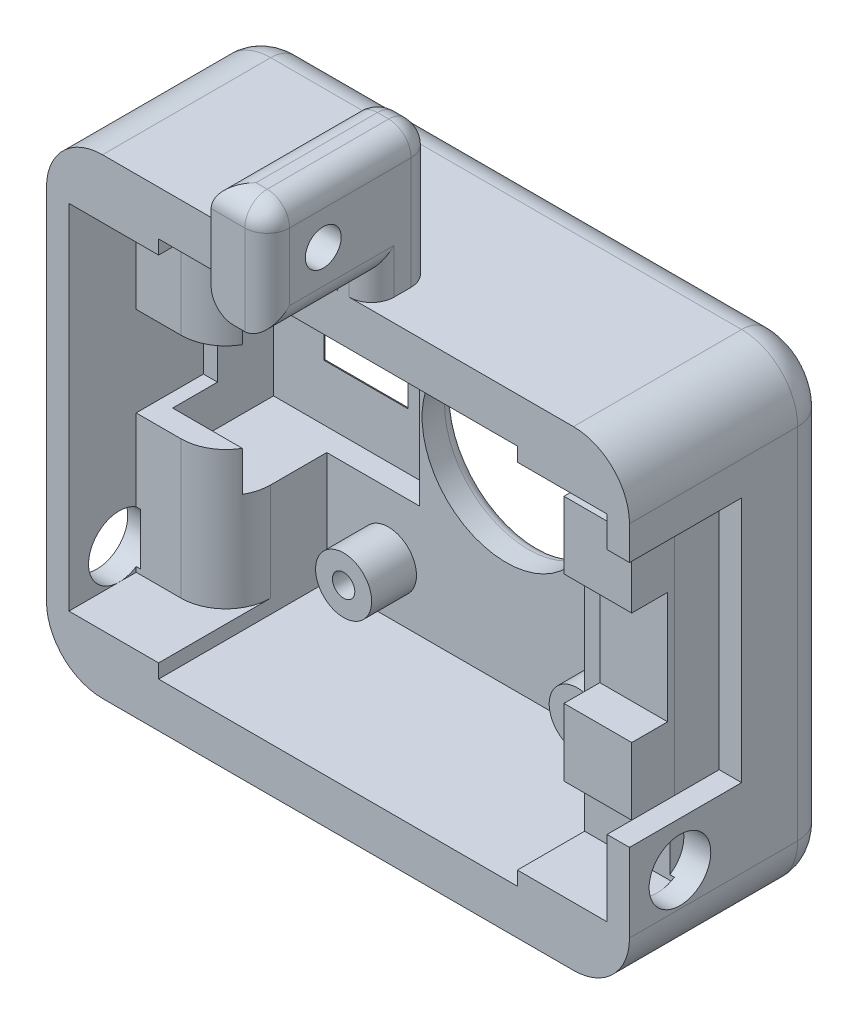
SolidWorks part; units mm, degrees
ref_plane "Front Plane" through (0, 0, 0) normal (0, 0, 1) x (1, 0, 0)
ref_plane "Top Plane" through (0, 0, 0) normal (0, 1, 0) x (1, 0, 0)
ref_plane "Right Plane" through (0, 0, 0) normal (1, 0, 0) x (0, 0, -1)
sketch "Sketch1" plane through (0, 0, 0) normal (0, 0, 1) x (1, 0, 0)
  line L1 (-26, 21) -> (26, 21)
  line L2 (-26, 21) -> (-26, -21)
  line L3 (-26, -21) -> (26, -21)
  line L4 (26, 21) -> (26, -21)
  line L5 (-26, 21) -> (26, -21) construction
  line L6 (-26, -21) -> (26, 21) construction
  point P0 (0, 0)
  dimension "D1" = 42
  dimension "D2" = 52
extrude "Boss-Extrude1" add sketch "Sketch1" along normal blind 10 contours L4 L3 L2 L1
sketch "Sketch2" plane through (0, 0, 10) normal (0, 0, 1) x (1, 0, 0)
  line L0 (-26, 21) -> (26, 21) construction
  line L1 (-24, 15.75) -> (24, 15.75)
  line L2 (-24, 15.75) -> (-24, -15.75)
  line L3 (-24, -15.75) -> (24, -15.75)
  line L4 (24, 15.75) -> (24, -15.75)
  line L5 (-24, 15.75) -> (24, -15.75) construction
  line L6 (-24, -15.75) -> (24, 15.75) construction
  line L7 (-26, -21) -> (26, -21) construction
  point P0 (0, 0)
  dimension "D1" = 5.25
  dimension "D2" = 48
  dimension "D3" = 5.25
extrude "Cut-Extrude1" cut sketch "Sketch2" against normal blind 6
sketch "Sketch6" plane through (0, 0, 0) normal (0, 0, -1) x (-1, 0, 0)
  line L1 (-26, 21) -> (26, 21)
  line L2 (-26, 21) -> (-26, -21)
  line L3 (-26, -21) -> (26, -21)
  line L4 (26, 21) -> (26, -21)
  line L5 (-26, 21) -> (26, -21) construction
  line L6 (-26, -21) -> (26, 21) construction
  point P0 (0, 0)
  dimension "D1" = 52
  dimension "D2" = 42
extrude "Boss-Extrude2" add sketch "Sketch6" along normal blind 8
sketch "Sketch5" plane through (0, 0, 4) normal (0, 0, 1) x (1, 0, 0)
  line L1 (-16, 17) -> (16, 17)
  line L2 (-16, 17) -> (-16, -17)
  line L3 (-16, -17) -> (16, -17)
  line L4 (16, 17) -> (16, -17)
  line L5 (-16, 17) -> (16, -17) construction
  line L6 (-16, -17) -> (16, 17) construction
  point P0 (0, 0)
  dimension "D1" = 34
  dimension "D2" = 32
extrude "Cut-Extrude5" cut sketch "Sketch5" against normal blind 9 and the other way through all
sketch "Sketch7" plane through (0, 0, -5) normal (0, 0, 1) x (1, 0, 0)
  circle A0 centre (0, 0) radius 7.5
  dimension "D1" = 15
extrude "Cut-Extrude4" cut sketch "Sketch7" against normal up to next
fillet "Fillet2" radius 1 1 edges at (-7.5, 0, -8)
fillet "Fillet3" radius 3 4 edges at (0, -21, -8) (-26, 0, -8) (26, 0, -8) (0, 21, -8)
fillet "Fillet4" radius 5 8 edges at (25.1213, 20.1213, -7.1213) (-25.1213, 20.1213, -7.1213) (-25.1213, -20.1213, -7.1213) (25.1213, -20.1213, -7.1213) (-26, 21, 2.5) (-26, -21, 2.5) (26, -21, 2.5) (26, 21, 2.5)
sketch "Sketch8" plane through (0, 0, 10) normal (0, 0, 1) x (1, 0, 0)
  line L0 (24, -15.75) -> (24, 15.75) construction
  line L5 (24, 13) -> (26, 13)
  line L6 (24, 13) -> (24, -9)
  line L7 (24, -9) -> (26, -9)
  line L8 (26, 13) -> (26, -9)
  line L9 (26, 16) -> (26, -16) construction
  line L10 (-21, 21) -> (21, 21) construction
  dimension "D1" = 22
  dimension "D2" = 8
extrude "Cut-Extrude6" cut sketch "Sketch8" against normal blind 10
sketch "Sketch11" plane through (0, 0, 4) normal (0, 0, 1) x (1, 0, 0)
  line L1 (24, 13) -> (17.954, 13)
  line L2 (24, 13) -> (24, -9)
  line L3 (24, -9) -> (17.954, -9)
  line L4 (17.954, 13) -> (17.954, -9)
  dimension "D1" = 6.046
  dimension "D2" = 22
extrude "Boss-Extrude9" add sketch "Sketch11" along normal blind 3.8 separate body
sketch "Sketch12" plane through (0, 0, 7.8) normal (0, 0, 1) x (1, 0, 0)
  line L0 (24, -9) -> (24, 13) construction
  line L1 (24, 7) -> (16.5, 7)
  line L2 (24, 7) -> (24, -3)
  line L3 (24, -3) -> (16.5, -3)
  line L4 (16.5, 7) -> (16.5, -3)
  line L5 (24, 13) -> (17.954, 13) construction
  line L7 (17.954, -9) -> (24, -9) construction
  dimension "D1" = 10
  dimension "D2" = 6
  dimension "D3" = 6
  dimension "D4" = 7.5
extrude "Cut-Extrude8" cut sketch "Sketch12" against normal blind 3.2
fillet "Fillet9" radius 4 1 edges at (-16, 0, 4)
sketch "Sketch13" plane through (26, 0, 0) normal (1, 0, 0) x (0, 0, -1)
  line L1 (-10, -9) -> (-10, -16) construction
  line L4 (-10, -16) -> (5, -16) construction
  circle A0 centre (-5.5, -13) radius 2.75
  dimension "D1" = 5.5
  dimension "D2" = 3
  dimension "D3" = 4.5
extrude "Cut-Extrude9" cut sketch "Sketch13" against normal blind 2.4
sketch "Sketch14" plane through (-26, 0, 0) normal (-1, 0, 0) x (0, 0, 1)
  line L1 (10, 16) -> (10, -16) construction
  line L2 (-5, -16) -> (10, -16) construction
  circle A0 centre (5.5, -13) radius 2.75
  dimension "D1" = 5.5
  dimension "D2" = 3
  dimension "D3" = 4.5
extrude "Cut-Extrude10" cut sketch "Sketch14" against normal blind 2.4
ref_plane "Plane2" through (0, 0, 2) normal (0, 0, -1) x (-1, 0, 0)
sketch "Sketch18" plane through (0, 0, 2) normal (0, 0, -1) x (-1, 0, 0)
  line L1 (-22.75, 7) -> (-7.75, 7)
  line L2 (-22.75, 7) -> (-22.75, -7)
  line L3 (-22.75, -7) -> (-7.75, -7)
  line L4 (-7.75, 7) -> (-7.75, -7)
  line L8 (7.75, 7) -> (22.75, 7)
  line L9 (7.75, 7) -> (7.75, -7)
  line L10 (7.75, -7) -> (22.75, -7)
  line L11 (22.75, 7) -> (22.75, -7)
  point P4 (-7.75, 0)
  dimension "D1" = 15
  dimension "D2" = 14
  dimension "D3" = 7.75
  dimension "D5" = 15
  dimension "D6" = 14
  dimension "D8" = 7.75
extrude "Cut-Extrude15" cut sketch "Sketch18" along normal blind 9
sketch "Sketch19" plane through (0, 0, -7) normal (0, 0, 1) x (1, 0, 0)
  line L1 (10.75, 2) -> (18.25, 2)
  line L2 (10.75, 2) -> (10.75, -2)
  line L3 (10.75, -2) -> (18.25, -2)
  line L4 (18.25, 2) -> (18.25, -2)
  line L7 (-18.25, 2) -> (-10.75, 2)
  line L8 (-18.25, 2) -> (-18.25, -2)
  line L9 (-18.25, -2) -> (-10.75, -2)
  line L10 (-10.75, 2) -> (-10.75, -2)
  line L12 (-7.75, 7) -> (-7.75, -7) construction
  line L13 (7.75, -7) -> (7.75, 7) construction
  point P6 (-10.75, 0)
  dimension "D1" = 7.5
  dimension "D2" = 4
  dimension "D3" = 3
  dimension "D5" = 7.5
  dimension "D6" = 4
  dimension "D7" = 3
extrude "Cut-Extrude16" cut sketch "Sketch19" against normal up to next (1 mm away)
sketch "Sketch21" plane through (0, 21, 0) normal (0, 1, 0) x (1, 0, 0)
  line L0 (-21, -10) -> (21, -10) construction
  line L1 (-2, -4.4799) -> (3, -4.4799)
  line L2 (-2, -4.4799) -> (-2, -10)
  line L3 (-2, -10) -> (3, -10)
  line L4 (3, -4.4799) -> (3, -10)
  line L5 (-26, -10) -> (-26, 5) construction
  dimension "D1" = 5
  dimension "D2" = 24
extrude "Boss-Extrude10" add sketch "Sketch21" along normal blind 2
sketch "Sketch27" plane through (0, 23, 0) normal (0, 1, 0) x (1, 0, 0)
  line L0 (-2, -4.4799) -> (-2, -10) construction
  line L1 (-2, -4.4799) -> (3, -4.4799)
  line L2 (-2, -4.4799) -> (-2, -19.3143)
  line L3 (-2, -19.3143) -> (3, -19.3143)
  line L4 (3, -4.4799) -> (3, -19.3143)
  line L5 (-2, -4.4799) -> (-2, -10) construction
  dimension "D1" = 14.8343
  dimension "D2" = 5
extrude "Boss-Extrude13" add sketch "Sketch27" along normal blind 10
sketch "Sketch28" plane through (-2, 0, 0) normal (-1, 0, 0) x (0, 0, 1)
  line L2 (19.3143, 33) -> (19.3143, 23) construction
  circle A0 centre (14.3143, 28) radius 1.6
  point P10 (19.3143, 28)
  dimension "D1" = 3.2
  dimension "D2" = 5
extrude "Cut-Extrude19" cut sketch "Sketch28" against normal through all
fillet "Fillet14" radius 2 11 edges at (0.5, 33, 4.4799) (3, 33, 11.8971) (0.5, 33, 19.3143) (-2, 33, 11.8971) (3, 27, 4.4799) (3, 28, 19.3143) (-2, 22, 10) (-2, 23, 14.6571) (-2, 27, 4.4799) (3, 23, 14.6571) (3, 22, 10)
fillet "Fillet13" radius 2 8 edges at (-18.25, 0, -8) (-10.75, 0, -8) (-14.5, -2, -8) (-14.5, 2, -8) (10.75, 0, -8) (18.25, 0, -8) (14.5, -2, -8) (14.5, 2, -8)
sketch "Sketch25" plane through (0, 0, -5) normal (0, 0, 1) x (1, 0, 0)
  line L0 (-10.5, 12.5) -> (10.5, 12.5) construction
  circle A0 centre (-10.5, 12.5) radius 2.5
  circle A1 centre (10.5, 12.5) radius 2.5
  circle A3 centre (-10.5, -12.5) radius 2.5
  circle A4 centre (10.3376, -12.5) radius 2.5
  point P4 (0, 12.5)
  dimension "D3" = 5
  dimension "D4" = 5
  dimension "D5" = 5
  dimension "D6" = 5
  dimension "D1" = 21
  dimension "D2" = 12.5
  dimension "D7" = 12.5
extrude "Boss-Extrude12" add sketch "Sketch25" along normal blind 4
sketch "Sketch26" plane through (0, 0, -1) normal (0, 0, 1) x (1, 0, 0)
  circle A0 centre (-10.5, 12.5) radius 1
  circle A1 centre (10.5, 12.5) radius 1
  circle A2 centre (-10.5, -12.5) radius 1
  circle A3 centre (10.3376, -12.5) radius 1
  dimension "D1" = 2
  dimension "D2" = 2
  dimension "D3" = 2
  dimension "D4" = 2
extrude "Cut-Extrude18" cut sketch "Sketch26" against normal blind 4
sketch "Sketch29" plane through (0, 0, 4) normal (0, 0, 1) x (1, 0, 0)
  line L0 (-16, 17) -> (-16, -17) construction
  line L1 (-24, 4.56) -> (-16, 4.56)
  line L2 (-24, 4.56) -> (-24, -3.44)
  line L3 (-24, -3.44) -> (-16, -3.44)
  line L4 (-16, 4.56) -> (-16, -3.44)
  dimension "D1" = 8
  dimension "D2" = 8
extrude "Cut-Extrude20" cut sketch "Sketch29" against normal blind 6
sketch "Sketch30" plane through (0, 17, 0) normal (0, -1, 0) x (1, 0, 0)
  line L0 (21, -5) -> (21, 10) construction
  line L1 (-13, 4.0639) -> (13, 4.0639)
  line L2 (-13, 4.0639) -> (-13, -4.9361)
  line L3 (-13, -4.9361) -> (13, -4.9361)
  line L4 (13, 4.0639) -> (13, -4.9361)
  line L6 (-21, -5) -> (-21, 10) construction
  dimension "D1" = 8
  dimension "D2" = 8
  dimension "D3" = 9
extrude "Cut-Extrude21" cut sketch "Sketch30" against normal blind 2
fillet "Chamfer1" radius 1 2 edges at (13, 17, -0.4361) (-13, 17, -0.4361) profile chamfer
